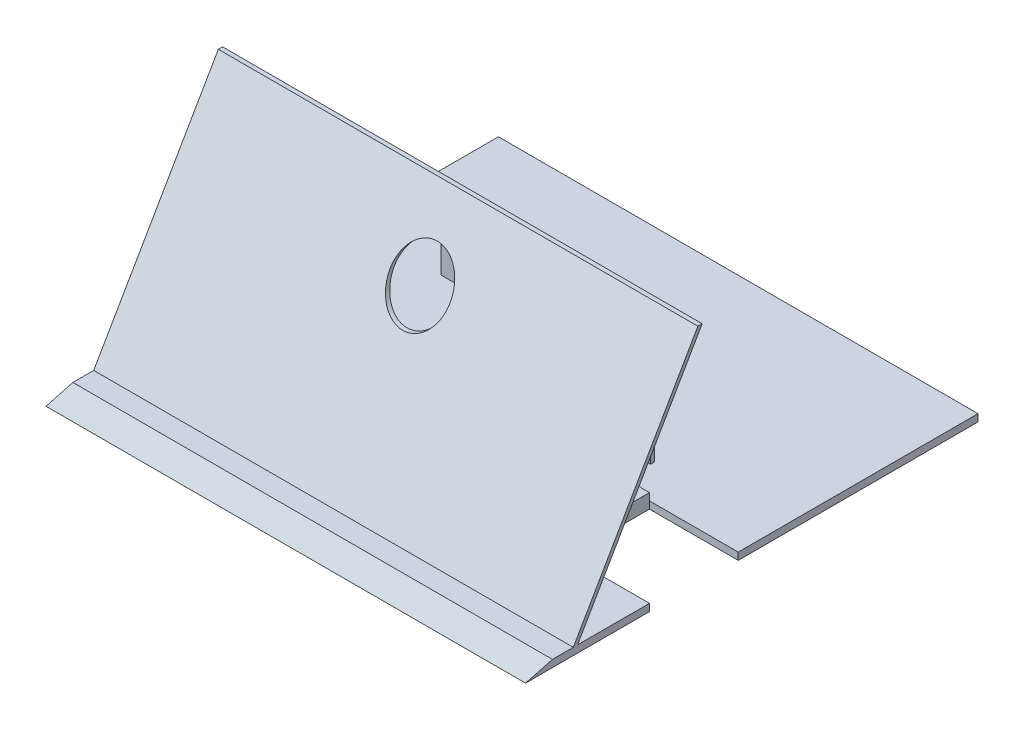
SolidWorks part; units mm, degrees
ref_plane "Alzado" through (0, 0, 0) normal (0, 0, 1) x (1, 0, 0)
ref_plane "Planta" through (0, 0, 0) normal (0, 1, 0) x (1, 0, 0)
ref_plane "Vista lateral" through (0, 0, 0) normal (1, 0, 0) x (0, 0, -1)
sketch "Croquis4" plane through (0, 0, 0) normal (0, 1, 0) x (1, 0, 0)
  line L1 (-100, 100) -> (100, 100) construction
  line L2 (-100, 100) -> (-100, -100) construction
  line L3 (-100, -100) -> (100, -100) construction
  line L4 (100, 100) -> (100, -100) construction
  line L5 (-100, 100) -> (100, -100) construction
  line L6 (-100, -100) -> (100, 100) construction
  point P0 (0, 0)
  dimension "D1" = 200
  dimension "D2" = 200
ref_plane "Plano1" through (0, -2, 0) normal (0, 1, 0) x (1, 0, 0)
ref_plane "Plano2" through (0, 0, 100) normal (0, 0, 1) x (1, 0, 0)
ref_axis "Eje1" through (-110, -2, 100) along (1, 0, 0)
sketch "Croquis5" plane through (0, 0, 0) normal (1, 0, 0) x (0, 0, -1)
  line L0 (-100, -2) -> (-69.0904, 6.2822)
  line L1 (-69.0904, 6.2822) -> (-68.8316, 5.3163)
  line L2 (-68.8316, 5.3163) -> (-96.1363, -2)
  line L3 (110, -2) -> (-110, -2) construction
  line L4 (-96.1363, -2) -> (-100, -2)
  line L5 (-88.6722, 0) -> (100, 0)
  line L6 (-100, 0) -> (100, 0) construction
  line L7 (100, 0) -> (-100, 0) construction
  line L8 (100, 0) -> (100, 3)
  line L9 (100, 3) -> (-77.476, 3)
  line L10 (-77.476, 3) -> (-88.6722, 0)
  dimension "D1" = 15
  dimension "D2" = 1
  dimension "D3" = 32
  dimension "D4" = 3
extrude "Saliente-Extruir2" add sketch "Croquis5" along normal mid plane 200 contours L8 L9 L2 L5 region at (0, 1.4847, -8.4344)
sketch "Croquis6" plane through (100, 0, 0) normal (1, 0, 0) x (0, 0, -1)
  line L0 (-68.776, 3) -> (-68.776, 17.261) construction
  line L1 (100, 3) -> (-77.476, 3) construction
  line L2 (-68.776, 3) -> (-16.8145, 93)
  line L3 (-16.8145, 93) -> (-15.0363, 93)
  line L4 (-15.0363, 93) -> (-66.9978, 3)
  line L5 (-66.9978, 3) -> (-68.776, 3)
  dimension "D1" = 8.7
  dimension "D2" = 60
  dimension "D3" = 1.54
  dimension "D4" = 90
extrude "Saliente-Extruir3" add sketch "Croquis6" against normal blind 200
sketch "Croquis11" plane through (0, 3, 0) normal (0, 1, 0) x (1, 0, 0)
  line L7 (100, -37) -> (-100.6699, -37) construction
  line L16 (100, 100) -> (100, -66.9978) construction
  line L17 (100, 0) -> (-100.5891, 0) construction
  line L18 (100, 100) -> (-100, 100) construction
  line L20 (100, -37) -> (63, -37)
  line L21 (100, -37) -> (100, 0)
  line L22 (100, 0) -> (63, 0)
  line L23 (63, -37) -> (63, 0)
  line L24 (-100.6699, -37) -> (-63.6699, -37)
  line L25 (-100.6699, -37) -> (-100.6699, 0)
  line L26 (-100.6699, 0) -> (-63.6699, 0)
  line L27 (-63.6699, -37) -> (-63.6699, 0)
  dimension "D1" = 100
  dimension "D2" = 37
  dimension "D3" = 37
  dimension "D4" = 37
extrude "Cortar-Extruir2" cut sketch "Croquis11" against normal through all
sketch "Croquis13" plane through (0, 3, 0) normal (0, 1, 0) x (1, 0, 0)
  line L1 (63, -37) -> (-63.6699, -37)
  line L2 (63, -37) -> (63, 0)
  line L3 (63, 0) -> (-63.6699, 0)
  line L4 (-63.6699, -37) -> (-63.6699, 0)
extrude "Saliente-Extruir9" add sketch "Croquis13" along normal blind 3
ref_plane "Plano3" through (0, 0, 35) normal (0, 0, 1) x (1, 0, 0)
ref_axis "Eje2" through (-110, 58.4218, 35) along (1, 0, 0)
sketch "Croquis14" plane through (0, 0, 35) normal (0, 0, 1) x (1, 0, 0)
  line L6 (0, -40.15) -> (0, 40.15) construction
  line L7 (50, 52.54) -> (-50, 52.54)
  line L8 (50, 52.54) -> (50, 51)
  line L9 (50, 51) -> (-50, 51)
  line L10 (-50, 52.54) -> (-50, 51)
  line L11 (-100, 3) -> (-63.6699, 3) construction
  point P6 (-50, 51.77)
  dimension "D1" = 1.54
  dimension "D2" = 100
  dimension "D3" = 50
  dimension "D4" = 48
extrude "Saliente-Extruir12" add sketch "Croquis14" against normal blind 50 separate body
sketch "Croquis20" plane through (0, 0, 35) normal (0, 0, 1) x (1, 0, 0)
  line L0 (-50, 51) -> (50, 51) construction
  line L1 (50, 52.54) -> (-49.9694, 52.54)
  line L2 (50, 52.54) -> (50, 51)
  line L3 (50, 51) -> (-49.9694, 51)
  line L4 (-49.9694, 52.54) -> (-49.9694, 51)
extrude "Saliente-Extruir13" add sketch "Croquis20" along normal up to next
sketch "Croquis21" plane through (0, 51, 0) normal (0, -1, 0) x (1, 0, 0)
  line L0 (50, 38.3959) -> (50, -15) construction
  line L1 (-50, -15) -> (50, -15)
  line L2 (-50, -15) -> (-50, -13.46)
  line L3 (-50, -13.46) -> (50, -13.46)
  line L4 (50, -15) -> (50, -13.46)
  dimension "D1" = 1.54
extrude "Saliente-Extruir14" add sketch "Croquis21" along normal up to next
sketch "Croquis22" plane through (0, 52.54, 0) normal (0, 1, 0) x (1, 0, 0)
  line L0 (50, 15) -> (-50, 15) construction
  line L1 (-12.5, -10) -> (12.5, -10)
  line L2 (-12.5, -10) -> (-12.5, -11.45)
  line L3 (-12.5, -11.45) -> (12.5, -11.45)
  line L4 (12.5, -10) -> (12.5, -11.45)
  line L5 (0, -51.15) -> (0, 51.15) construction
  dimension "D1" = 25
  dimension "D2" = 1.45
  dimension "D3" = 25
  dimension "D4" = 12.5
extrude "Saliente-Extruir15" add sketch "Croquis22" along normal blind 25
sketch "Croquis23" plane through (0, 0, 10) normal (0, 0, -1) x (-1, 0, 0)
  line L0 (0, 51.15) -> (0, -51.15) construction
  line L1 (-12.5, 77.54) -> (12.5, 77.54) construction
  circle A0 centre (0, 65.54) radius 9.5
  dimension "D1" = 19
  dimension "D2" = 12
extrude "Cortar-Extruir9" cut sketch "Croquis23" against normal blind 1.45
sketch "Croquis24" plane through (0, 0, 35) normal (0, 0, 1) x (1, 0, 0)
  circle A0 centre (0, 65.54) radius 12.5
  dimension "D1" = 25
extrude "Cortar-Extruir10" cut sketch "Croquis24" against normal mid plane 25
